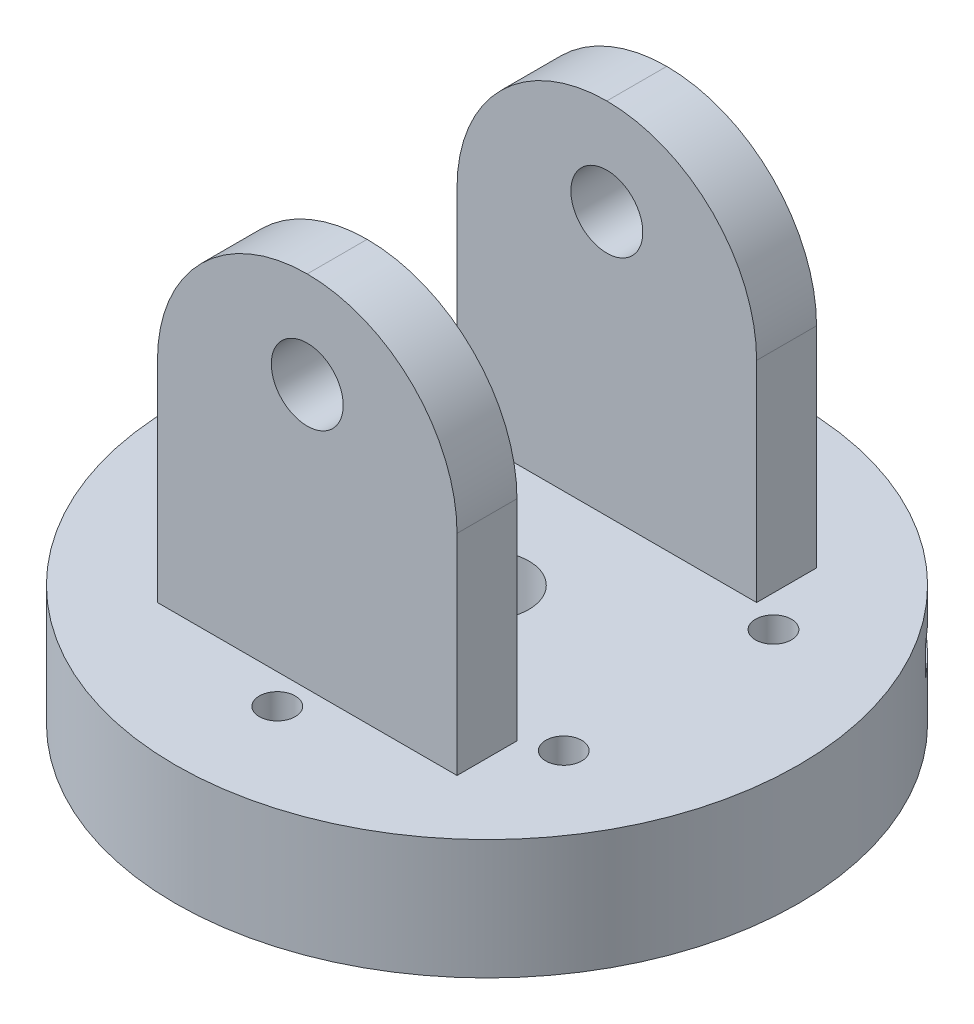
SolidWorks part; units mm, degrees
material "PLA personnalisé"
ref_plane "Plan de face" through (0, 0, 0) normal (0, 0, 1) x (1, 0, 0)
ref_plane "Plan de dessus" through (0, 0, 0) normal (0, 1, 0) x (1, 0, 0)
ref_plane "Plan de droite" through (0, 0, 0) normal (1, 0, 0) x (0, 0, -1)
sketch "Esquisse1" plane through (0, 0, 0) normal (0, 1, 0) x (1, 0, 0)
  circle A0 centre (0, 0) radius 52
  circle A1 centre (0, 0) radius 7
  dimension "D1" = 104
  dimension "D2" = 14
extrude "Boss.-Extru.1" add sketch "Esquisse1" along normal blind 20
sketch "Esquisse2" plane through (0, 20, 0) normal (0, 1, 0) x (1, 0, 0)
  line L0 (0, 0) -> (0, 25) construction
  line L1 (25, 20) -> (-25, 20)
  line L2 (25, 20) -> (25, 30)
  line L3 (-25, 20) -> (-25, 30)
  line L4 (25, 30) -> (-25, 30)
  line L5 (25, 20) -> (-25, 30) construction
  line L6 (-25, 20) -> (25, 30) construction
  line L7 (-34.3845, 0) -> (33.9668, 0) construction
  dimension "D1" = 25
  dimension "D2" = 50
  dimension "D3" = 10
extrude "Boss.-Extru.2" add sketch "Esquisse2" along normal blind 60
fillet "Congé1" radius 25 2 edges at (25, 80, -25) (-25, 80, -25)
sketch "Esquisse3" plane through (0, 0, -30) normal (0, 0, -1) x (-1, 0, 0)
  line L1 (25, 55) -> (25, 20) construction
  line L2 (-25, 20) -> (25, 20) construction
  circle A0 centre (0, 64) radius 6
  dimension "D1" = 44
  dimension "D2" = 12
  dimension "D3" = 25
extrude "Enlèv. mat.-Extru.1" cut sketch "Esquisse3" against normal blind 40
pattern_circular "Répétition circulaire1" count 2 over 360 about axis through (0, 20, 0) along (0, 1, 0) of "Boss.-Extru.2", "Congé1", "Enlèv. mat.-Extru.1"
sketch "Esquisse5" plane through (0, 0, 0) normal (0, -1, 0) x (1, 0, 0)
  circle A0 centre (0, 0) radius 35 construction
  circle A1 centre (0, 35) radius 1.6
  dimension "D1" = 70
  dimension "D2" = 3.2
extrude "Enlèv. mat.-Extru.2" cut sketch "Esquisse5" against normal blind 20
pattern_circular "Répétition circulaire2" count 6 over 360 about axis through (0, 0, 0) along (0, 1, 0) of "Enlèv. mat.-Extru.2"
sketch "Esquisse6" plane through (0, 20, 0) normal (0, 1, 0) x (1, 0, 0)
  circle A0 centre (30.3109, 17.5) radius 3
  circle A1 centre (30.3109, -17.5) radius 3
  circle A2 centre (0, -35) radius 3
  circle A3 centre (-30.3109, -17.5) radius 3
  circle A4 centre (-30.3109, 17.5) radius 3
  circle A5 centre (0, 35) radius 3
  point P16 (0, 0)
  dimension "D1" = 6
  dimension "D2" = 6
extrude "Enlèv. mat.-Extru.3" cut sketch "Esquisse6" against normal blind 11
sketch "Esquisse7" plane through (0, 0, 0) normal (0, 0, 1) x (1, 0, 0)
  line L0 (52, 20) -> (-52, 20) construction
  line L1 (-40.05, 10) -> (40.05, 10)
  line L2 (-40.05, 10) -> (-40.05, 15)
  line L3 (-40.05, 15) -> (40.05, 15)
  line L4 (40.05, 10) -> (40.05, 15)
  line L5 (-40.05, 10) -> (40.05, 15) construction
  line L6 (-40.05, 15) -> (40.05, 10) construction
  line L7 (0, 0) -> (0, 86.6034) construction
  point P4 (0, 12.5)
  point P10 (0, 0)
  dimension "D1" = 5
  dimension "D2" = 5
  dimension "D3" = 80.1
extrude "Enlèv. mat.-Extru.4" cut sketch "Esquisse7" against normal blind 45 from offset 10 offset against normal yes
